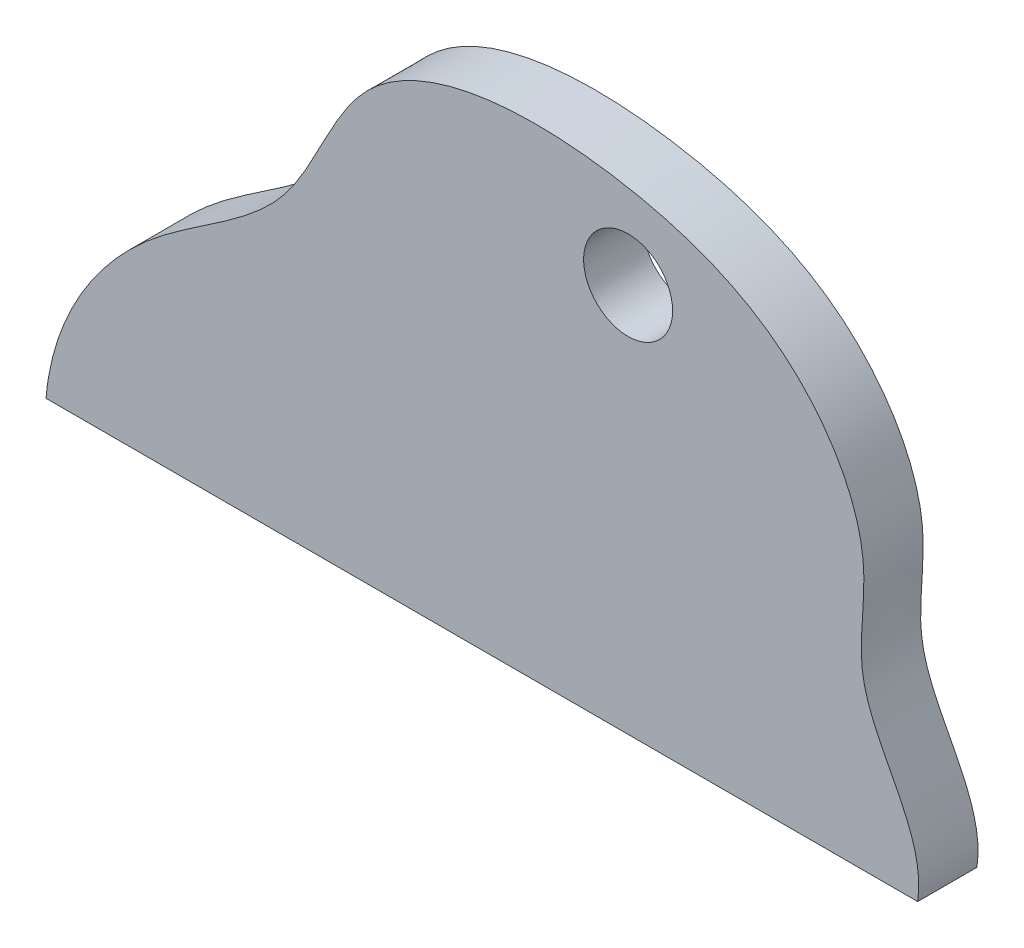
SolidWorks part; units mm, degrees
ref_plane "Front Plane" through (0, 0, 0) normal (0, 0, 1) x (1, 0, 0)
ref_plane "Top Plane" through (0, 0, 0) normal (0, 1, 0) x (1, 0, 0)
ref_plane "Right Plane" through (0, 0, 0) normal (1, 0, 0) x (0, 0, -1)
sketch "Sketch1" plane through (0, 0, 0) normal (0, 0, 1) x (1, 0, 0)
  line L0 (108.3333, 216) -> (541.6667, 216) construction
  line L1 (414.6641, 28.838) -> (477.7452, 28.838)
  circle A0 centre (456.7909, 56.9953) radius 1.905
  spline S0 degree 3 poles (414.6641, 28.838) (415.1532, 34.395) (420.4857, 42.9226) (432.8588, 48.7498) (437.3367, 63.8121) (455.661, 64.6706) (469.273, 59.1194) (474.8394, 49.0661) (472.3409, 38.7746) (478.4199, 33.32) (477.7452, 28.838) knots 0 0 0 0 0.159469 0.276153 0.381296 0.572074 0.709165 0.806266 0.876509 1 1 1 1
  dimension "D20" = 3.81
  dimension "D1" = 414.6641
  dimension "D2" = 416.6286
  dimension "D3" = 422.5219
  dimension "D4" = 431.9077
  dimension "D5" = 437.5828
  dimension "D6" = 456.7909
  dimension "D7" = 469.4508
  dimension "D8" = 473.8163
  dimension "D9" = 475.999
  dimension "D10" = 477.7452
  dimension "D11" = 28.838
  dimension "D12" = 35.6044
  dimension "D13" = 40.843
  dimension "D14" = 42.8075
  dimension "D15" = 48.046
  dimension "D16" = 50.2288
  dimension "D17" = 56.9953
  dimension "D18" = 59.3963
  dimension "D19" = 63.1069
extrude "Boss-Extrude1" add sketch "Sketch1" along normal blind 4.292
scale "Scale1" scale about centroid uniform scaling yes scale factor 0.739744
sketch "Sketch2" plane through (0, 0, 3.7335) normal (0, 0, 1) x (1, 0, 0)
  circle A0 centre (454.7509, 53.4158) radius 2.3813
  dimension "D1" = 4.7625
extrude "Cut-Extrude1" cut sketch "Sketch2" against normal through all
